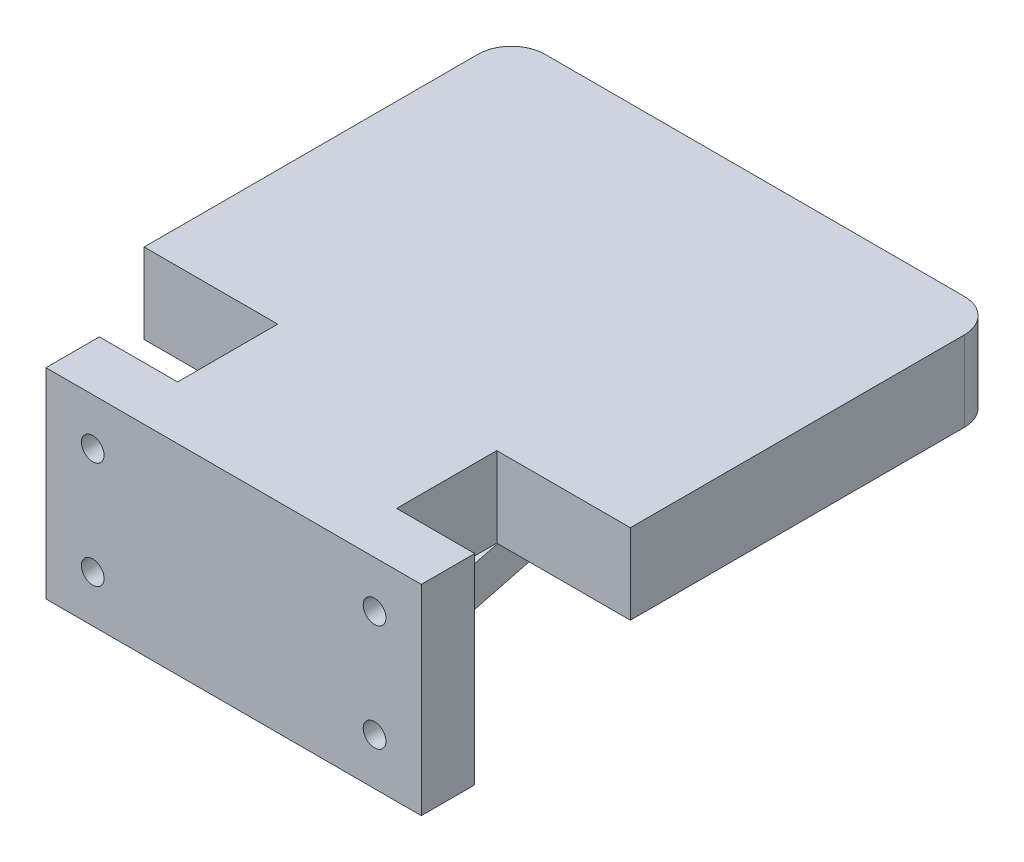
SolidWorks part; units mm, degrees
ref_plane "Front Plane" through (0, 0, 0) normal (0, 0, 1) x (1, 0, 0)
ref_plane "Top Plane" through (0, 0, 0) normal (0, 1, 0) x (1, 0, 0)
ref_plane "Right Plane" through (0, 0, 0) normal (1, 0, 0) x (0, 0, -1)
sketch "Sketch1" plane through (0, 0, 0) normal (0, 0, 1) x (1, 0, 0)
  line L0 (0, 0) -> (56.2, 0)
  line L1 (28.1, -5.5) -> (28.1, -10) construction
  line L2 (0, 0) -> (0, -30)
  line L3 (0, -30) -> (56.2, -30)
  line L5 (56.2, 0) -> (56.2, -30)
  line L8 (35.8259, -3) -> (37.9889, -3) construction
  line L18 (0, -15) -> (56.2, -15) construction
  arc A0 (19.5099, 0) -> (37.9889, -3) centre (28.1, -5.5) ccw construction
  arc A1 (35.8259, 0) -> (35.8259, -3) centre (35.8259, -1.5) ccw construction
  dimension "D4" = 30
  dimension "D5" = 1.5
  dimension "D1" = 10.2
  dimension "D3" = 56.2
extrude "Boss-Extrude1" add sketch "Sketch1" along normal blind 5
sketch "Sketch3" plane through (0, 0, 5) normal (0, 0, 1) x (1, 0, 0)
  line L0 (0, 0) -> (0, -30)
  line L1 (0, -30) -> (56.2, -30)
  line L2 (56.2, -30) -> (56.2, 0) construction
  line L3 (0, 0) -> (56.2, 0)
  line L4 (56.2, 0) -> (56.2, -30)
extrude "Boss-Extrude2" add sketch "Sketch3" along normal blind 3
sketch "Sketch4" plane through (0, 0, 0) normal (0, 0, -1) x (-1, 0, 0)
  line L0 (-56.2, -15) -> (0, -15) construction
  line L1 (-56.2, -30) -> (-56.2, 0) construction
  line L2 (0, 0) -> (0, -30) construction
  circle A0 centre (-49.2, -7) radius 1.7
  circle A1 centre (-7, -7) radius 1.7
  circle A2 centre (-7, -23) radius 1.7
  circle A3 centre (-49.2, -23) radius 1.7
  dimension "D1" = 3.4
  dimension "D2" = 49.2
  dimension "D3" = 7
extrude "Cut-Extrude2" cut sketch "Sketch4" against normal up to surface (8 mm away) up to face at (28.1, -15, 8)
sketch "Sketch5" plane through (0, 0, 0) normal (0, 1, 0) x (1, 0, 0)
  line L0 (0, 0) -> (7, 0) construction
  line L1 (56.2, 0) -> (0, 0) construction
  line L2 (7, 0) -> (8.7, 0) construction
  line L3 (8.7, 0) -> (11.7, 0) construction
  line L4 (28.1, 0) -> (28.1, -8) construction
  line L5 (56.2, -8) -> (0, -8) construction
  line L6 (44.5, 0) -> (11.7, 0)
  line L7 (11.7, 0) -> (11.7, 15)
  line L10 (11.7, 15) -> (-8.3, 15)
  line L11 (-8.3, 15) -> (-8.3, 65)
  line L12 (-3.3, 70) -> (59.5, 70)
  line L13 (44.5, 0) -> (44.5, 15)
  line L14 (64.5, 15) -> (64.5, 65)
  line L15 (44.5, 15) -> (64.5, 15)
  arc A2 (-8.3, 65) -> (-3.3, 70) centre (-3.3, 65) cw
  arc A3 (64.5, 65) -> (59.5, 70) centre (59.5, 65) ccw
  point P17 (-8.3, 70)
  point P24 (28.1, 70)
  point P25 (64.5, 70)
  dimension "D5" = 20
  dimension "D7" = 5
  dimension "D1" = 7
  dimension "D2" = 1.7
  dimension "D3" = 3
  dimension "D4" = 15
  dimension "D6" = 55
extrude "Boss-Extrude3" add sketch "Sketch5" against normal blind 12
ref_plane "Plane1" through (28.1, 0, 0) normal (1, 0, 0) x (0, 0, -1)
sketch "Sketch6" plane through (28.1, 0, 0) normal (1, 0, 0) x (0, 0, -1)
  line L4 (0, -12) -> (0, -30)
  line L5 (0, -12) -> (15, -12) construction
  line L6 (0, -30) -> (70, -12)
  line L7 (70, -12) -> (0, -12)
extrude "Boss-Extrude4" add sketch "Sketch6" along normal blind 10 and the other way blind 10
sketch "Sketch7" plane through (28.1, 0, 0) normal (1, 0, 0) x (0, 0, -1)
  line L0 (8, -12) -> (8, -22)
  line L1 (70, -12) -> (0, -12) construction
  line L3 (8, -12) -> (46.8889, -12)
  line L5 (8, -22) -> (46.8889, -12)
  line L6 (0, -30) -> (70, -12) construction
  dimension "D1" = 8
  dimension "D2" = 10
  dimension "D3" = 38.8889
extrude "Cut-Extrude3" cut sketch "Sketch7" against normal up to next and the other way up to next
sketch "Sketch8" plane through (0, 0, 0) normal (0, 0, -1) x (-1, 0, 0)
  line L3 (-56.2, -15) -> (0, -15) construction
  line L4 (-56.2, -30) -> (-56.2, 0) construction
  line L5 (0, 0) -> (0, -30) construction
  circle A0 centre (-49.2, -7) radius 2.6
  circle A1 centre (-7, -7) radius 2.6
  circle A2 centre (-7, -23) radius 2.6
  circle A3 centre (-49.2, -23) radius 2.6
  dimension "D1" = 5.2
extrude "Cut-Extrude4" cut sketch "Sketch8" against normal blind 4
